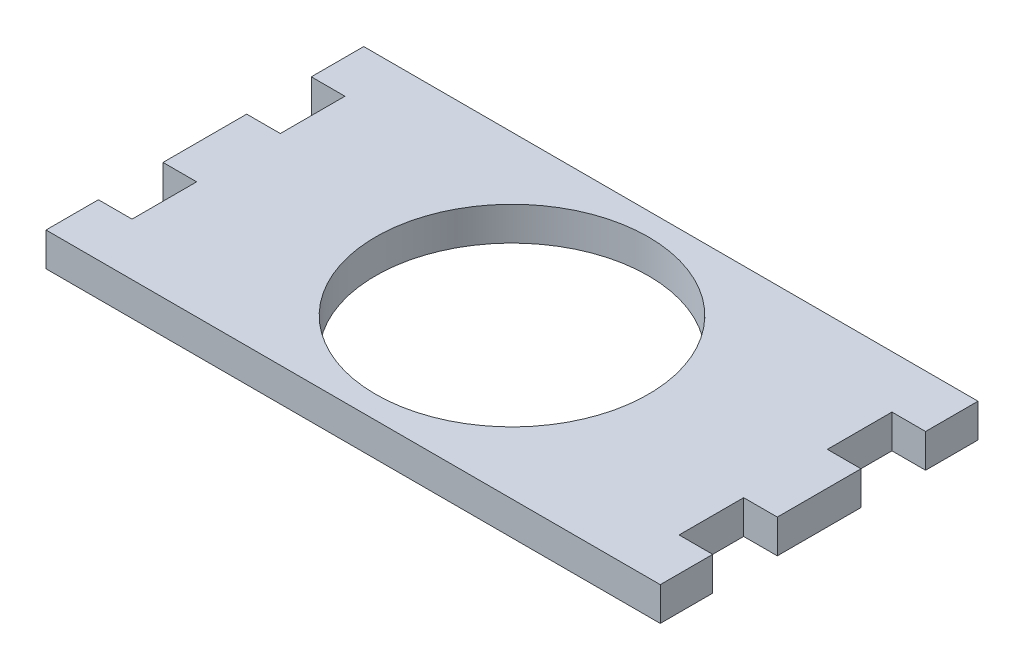
SolidWorks part; units mm, degrees
ref_plane "Front Plane" through (0, 0, 0) normal (0, 0, 1) x (1, 0, 0)
ref_plane "Top Plane" through (0, 0, 0) normal (0, 1, 0) x (1, 0, 0)
ref_plane "Right Plane" through (0, 0, 0) normal (1, 0, 0) x (0, 0, -1)
sketch "Sketch1" plane through (0, 0, 0) normal (0, 1, 0) x (1, 0, 0)
  line L0 (-29, 0) -> (0, 0) construction
  line L1 (-29, 15) -> (29, 15)
  line L2 (-29, 15) -> (-29, 10.05)
  line L3 (-29, -15) -> (29, -15)
  line L5 (0, 15) -> (0, -15) construction
  line L6 (29, -10.05) -> (29, -15)
  line L7 (29, -10.05) -> (25.825, -10.05)
  line L8 (-29, -10.05) -> (-25.825, -10.05)
  line L9 (-25.825, -10.05) -> (-25.825, -3.95)
  line L10 (-25.825, -3.95) -> (-29, -3.95)
  line L11 (-29, 3.95) -> (-29, -3.95)
  line L12 (-29, -10.05) -> (-29, -15)
  line L13 (-29, 10.05) -> (-25.825, 10.05)
  line L14 (-25.825, 10.05) -> (-25.825, 3.95)
  line L15 (-25.825, 3.95) -> (-29, 3.95)
  line L16 (25.825, -10.05) -> (25.825, -3.95)
  line L17 (25.825, -3.95) -> (29, -3.95)
  line L18 (29, 3.95) -> (29, -3.95)
  line L19 (25.825, 3.95) -> (29, 3.95)
  line L20 (25.825, 10.05) -> (25.825, 3.95)
  line L21 (29, 10.05) -> (25.825, 10.05)
  line L22 (29, 15) -> (29, 10.05)
  circle A0 centre (0, 0) radius 12.875
  dimension "D1" = 25.75
  dimension "D2" = 3.175
  dimension "D3" = 7.9
  dimension "D4" = 6.1
  dimension "D5" = 29
  dimension "D6" = 30
  dimension "D7" = 58
  dimension "D8" = 20.1
extrude "Boss-Extrude1" add sketch "Sketch1" along normal blind 3.175
